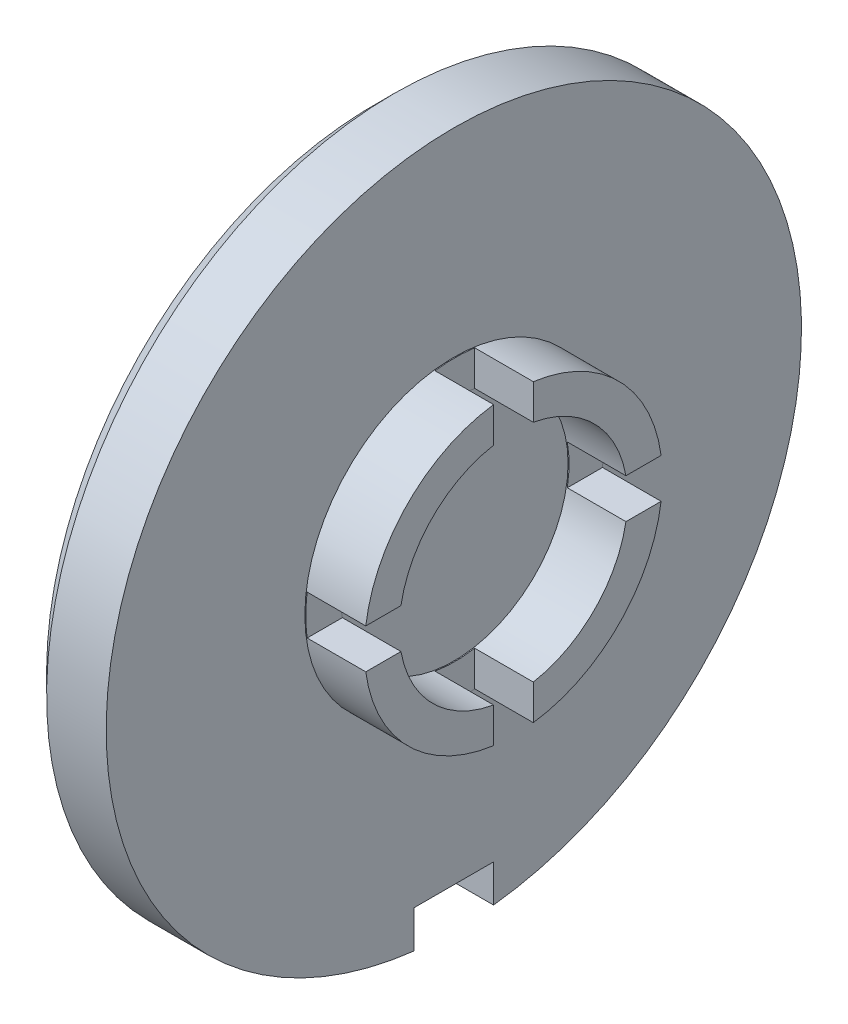
SolidWorks part; units mm, degrees
ref_plane "Front Plane" through (0, 0, 0) normal (0, 0, 1) x (1, 0, 0)
ref_plane "Top Plane" through (0, 0, 0) normal (0, 1, 0) x (1, 0, 0)
ref_plane "Right Plane" through (0, 0, 0) normal (1, 0, 0) x (0, 0, -1)
ref_plane "Plane1" through (0, 0, 66) normal (0, 0, 1) x (1, 0, 0)
sketch "Sketch1" plane through (0, 0, 66) normal (0, 0, 1) x (1, 0, 0)
  line L0 (-90.6, -65) -> (-77.8, -65) construction
  line L1 (-82.8, -62.7) -> (-84, -62.7)
  line L2 (-84, -62.7) -> (-84, -65)
  line L3 (-84, -65) -> (-85.6, -65)
  line L4 (-85.6, -65) -> (-85.6, -58.4)
  line L5 (-85.6, -58.4) -> (-85.2, -58)
  line L6 (-85.2, -58) -> (-84, -58)
  line L7 (-84, -58) -> (-84, -62)
  line L8 (-84, -62) -> (-82.8, -62)
  line L9 (-82.8, -62) -> (-82.8, -62.7)
revolve "Revolve1" add sketch "Sketch1" angle 360 about L0
sketch "Sketch2" plane through (0, 0, 0) normal (0, 0, 1) x (1, 0, 0)
  line L1 (-83.98, -65.4) -> (-82.7, -65.4)
  line L2 (-83.98, -65.4) -> (-83.98, -64.6)
  line L3 (-83.98, -64.6) -> (-82.7, -64.6)
  line L4 (-82.7, -65.4) -> (-82.7, -64.6)
extrude "Boss-Extrude1" add sketch "Sketch2" along normal blind 6.4 from offset 62.8 separate body
combine bodies "Combine1" operation type subtract main body 101 bodies to subtract 102
sketch "Sketch3" plane through (0, 0, 0) normal (0, 0, 1) x (1, 0, 0)
  line L1 (-83.98, -68.2) -> (-82.7, -68.2)
  line L2 (-83.98, -68.2) -> (-83.98, -61.8)
  line L3 (-83.98, -61.8) -> (-82.7, -61.8)
  line L4 (-82.7, -68.2) -> (-82.7, -61.8)
extrude "Boss-Extrude2" add sketch "Sketch3" along normal blind 0.8 from offset 65.6 separate body
combine bodies "Combine2" operation type subtract main body 103 bodies to subtract 104
sketch "Sketch4" plane through (0, 0, 0) normal (0, 0, 1) x (1, 0, 0)
  line L1 (-85.7, -72.1) -> (-83.9, -72.1)
  line L2 (-85.7, -72.1) -> (-85.7, -71.2)
  line L3 (-85.7, -71.2) -> (-83.9, -71.2)
  line L4 (-83.9, -72.1) -> (-83.9, -71.2)
extrude "Boss-Extrude3" add sketch "Sketch4" along normal blind 1.6 from offset 65.2 separate body
combine bodies "Combine3" operation type subtract main body 105 bodies to subtract 106
